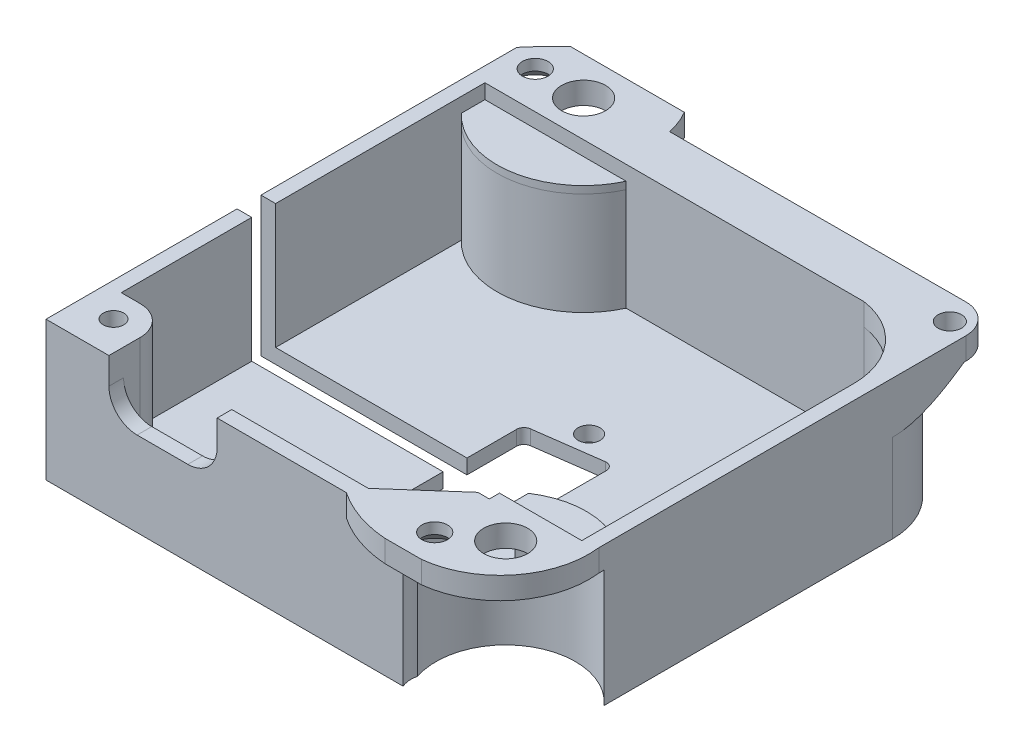
SolidWorks part; units mm, degrees
ref_plane "Спереди" through (0, 0, 0) normal (0, 0, 1) x (1, 0, 0)
ref_plane "Сверху" through (0, 0, 0) normal (0, 1, 0) x (1, 0, 0)
ref_plane "Справа" through (0, 0, 0) normal (1, 0, 0) x (0, 0, -1)
sketch "Sketch1" plane through (0, -19.7, 0) normal (0, 1, 0) x (1, 0, 0)
  line L0 (-32.5, -24.6) -> (-32.5, -32.9854)
  line L1 (-32.5, -32.9854) -> (7.4639, -32.9854)
  line L2 (7.4639, -32.9854) -> (16.9694, -24.6)
  line L45 (28.1923, 12.3774) -> (28.1923, -24.6)
  line L46 (28.1923, -24.6) -> (16.9694, -24.6)
  line L52 (14.473, -37.75) -> (19.5, -37.75)
  line L53 (30.1923, -24.25) -> (30.1923, 29.8047)
  line L54 (30.1923, 29.8047) -> (-14.1412, 29.6964)
  line L55 (-15.4145, 32.9914) -> (-30.9271, 32.9914)
  line L56 (-34.5, 29.2347) -> (-34.5, -5.6693)
  line L57 (-34.5, -5.6693) -> (-32.5, -5.6693)
  line L58 (-32.5, -5.6693) -> (-32.5, 22.8774)
  line L59 (-32.5, 22.8774) -> (19.1923, 22.8774)
  line L87 (-34.5, -34.9854) -> (6.4639, -34.9854)
  line L90 (-32.5, -24.6) -> (-32.5, -8.9249)
  line L91 (-32.5, -8.9249) -> (-34.5, -8.9249)
  line L92 (-34.5, -8.9249) -> (-34.5, -34.9854)
  arc A0 (14.473, -37.75) -> (6.4639, -34.9854) centre (15.6402, -21.385) cw
  circle A1 centre (27.4031, 26.3884) radius 1.6
  circle A10 centre (-23.9566, 27.7968) radius 3
  circle A11 centre (-30.7077, 27.9532) radius 1.75
  circle A12 centre (23.0406, -29.8242) radius 3
  circle A13 centre (17.1804, -33.65) radius 1.75
  arc A15 (19.5, -37.75) -> (30.1923, -24.25) centre (18.1591, -25.7037) ccw
  arc A17 (-14.1412, 29.6964) -> (-15.4145, 32.9914) centre (-23.9566, 27.7968) ccw
  arc A18 (-30.9271, 32.9914) -> (-34.5, 29.2347) centre (0, 0) ccw
  arc A19 (28.1923, 12.3774) -> (19.1923, 22.8774) centre (17.6928, 12.485) ccw
  dimension "D2" = 6
  dimension "D3" = 2
  dimension "D4" = 2
  dimension "D6" = 2
extrude "Boss-Extrude1" add sketch "Sketch1" against normal blind 3
sketch "Sketch2" plane through (0, -22.7, 0) normal (0, -1, 0) x (1, 0, 0)
  line L0 (-34.5, -25.75) -> (20.1923, -25.75)
  line L1 (-34.5, -29.2347) -> (-34.5, 5.6693) construction
  line L2 (30.1923, 24.25) -> (30.1923, -29.8047) construction
  line L3 (-32.5, 24.6) -> (-32.5, 32.9854)
  line L4 (19.1923, -22.8774) -> (-32.5, -22.8774)
  line L5 (-32.5, 32.9854) -> (7.4639, 32.9854)
  line L6 (-32.5, -22.8774) -> (-32.5, 5.6693)
  line L7 (16.9694, 24.6) -> (7.4639, 32.9854) construction
  line L8 (-32.5, 5.6693) -> (-34.5, 5.6693)
  line L9 (-34.5, 5.6693) -> (-34.5, -25.75)
  line L10 (30.1923, -15.75) -> (30.1923, 25.1)
  line L11 (28.1923, -13.8774) -> (28.1923, 24.6)
  line L12 (7.4639, 32.9854) -> (-32.5, 32.9854) construction
  line L13 (7.4639, 32.9854) -> (16.9694, 24.6)
  line L14 (16.9694, 24.6) -> (28.1923, 24.6)
  line L16 (-32.5, 24.6) -> (-32.5, 8.9249)
  line L17 (-32.5, 8.9249) -> (-34.5, 8.9249)
  line L18 (-34.5, 8.9249) -> (-34.5, 34.9854) construction
  line L20 (-34.5, 8.9249) -> (-34.5, 34.9854)
  line L21 (-34.5, 34.9854) -> (6.4639, 34.9854) construction
  line L22 (30.1923, 25.1) -> (30.1923, 26.25)
  line L23 (-34.5, 34.9854) -> (30.1923, 34.9854)
  line L24 (30.1923, 34.9854) -> (30.1923, 26.25)
  arc A0 (20.1923, -25.75) -> (30.1923, -15.75) centre (20.1923, -15.75) ccw
  arc A1 (28.1923, -13.8774) -> (19.1923, -22.8774) centre (19.1923, -13.8774) cw
extrude "Boss-Extrude2" add sketch "Sketch2" along normal blind 14
sketch "Sketch3" plane through (0, -36.7, 0) normal (0, -1, 0) x (1, 0, 0)
  line L15 (-6.3971, 15.146) -> (-6.3971, 8.9249)
  line L16 (3.4678, 17.3642) -> (-5.5322, 16.1369)
  line L17 (4.6029, -2.3354) -> (4.6029, 16.3733)
  line L18 (-5.5322, -2.099) -> (3.4678, -3.3263)
  line L19 (-6.3971, 5.6693) -> (-6.3971, -1.1082)
  line L36 (-34.5, 5.6693) -> (-34.5, -25.75)
  line L37 (-34.5, -25.75) -> (20.1923, -25.75)
  line L38 (30.1923, -15.75) -> (30.1923, 34.9854)
  line L39 (30.1923, 34.9854) -> (-34.5, 34.9854)
  line L40 (-34.5, 34.9854) -> (-34.5, 8.9249)
  line L41 (-34.5, 8.9249) -> (-6.3971, 8.9249)
  line L47 (-6.3971, 5.6693) -> (-34.5, 5.6693)
  arc A6 (20.1923, -25.75) -> (30.1923, -15.75) centre (20.1923, -15.75) ccw
  arc A13 (-5.5322, 16.1369) -> (-6.3971, 15.146) centre (-5.3971, 15.146) ccw
  arc A14 (4.6029, 16.3733) -> (3.4678, 17.3642) centre (3.6029, 16.3733) ccw
  arc A15 (3.4678, -3.3263) -> (4.6029, -2.3354) centre (3.6029, -2.3354) ccw
  arc A16 (-6.3971, -1.1082) -> (-5.5322, -2.099) centre (-5.3971, -1.1082) ccw
  circle A38 centre (-0.8971, -5.4811) radius 1.5
  circle A41 centre (-0.8971, 19.5189) radius 1.5
extrude "Boss-Extrude3" add sketch "Sketch3" along normal blind 2
sketch "Sketch16" plane through (0, -36.7, 0) normal (0, 1, 0) x (1, 0, 0)
  line L2 (28.1923, -20.1051) -> (28.1923, -21.8423)
  line L3 (12.0418, -29.9854) -> (13.542, -29.9854)
  arc A0 (28.1923, -21.8423) -> (13.542, -29.9854) centre (23.0406, -29.8242) ccw
  arc A2 (12.0418, -29.9854) -> (28.1923, -20.1051) centre (23.0406, -29.8242) cw
extrude "Boss-Extrude26" add sketch "Sketch16" along normal up to surface (14 mm away) up to face at (24.3136, -22.7, -18.5705)
sketch "Sketch17" plane through (0, -22.7, 0) normal (0, 1, 0) x (1, 0, 0)
  line L0 (12.0783, -28.9148) -> (16.9694, -28.9148)
  line L2 (16.9694, -28.9148) -> (16.9694, -24.6)
  line L3 (16.9694, -24.6) -> (28.1923, -24.6)
  line L4 (28.1923, -24.6) -> (28.1923, -20.1051)
  arc A3 (28.1923, -20.1051) -> (12.0783, -28.9148) centre (23.0406, -29.8242) ccw
extrude "Boss-Extrude27" add sketch "Sketch17" along normal blind 1
sketch "Sketch4" plane through (0, -22.7, 0) normal (0, -1, 0) x (1, 0, 0)
  circle A0 centre (23.0406, 29.8242) radius 9.5
  circle A1 centre (-23.9566, -27.7968) radius 9.7968
extrude "Cut-Extrude1" cut sketch "Sketch4" along normal blind 30
sketch "Sketch5" plane through (0, 0, 34.9854) normal (0, 0, 1) x (1, 0, 0)
  line L0 (8.9694, -30.7) -> (8.9694, -19.7)
  line L1 (-34.5, -19.7) -> (6.4639, -19.7) construction
  line L2 (16.9694, -30.7) -> (16.9694, -19.7)
  line L3 (14.473, -19.7) -> (19.5, -19.7) construction
  line L4 (16.9694, -19.7) -> (8.9694, -19.7)
  line L5 (10.9694, -32.7) -> (14.9694, -32.7)
  arc A0 (16.9694, -30.7) -> (14.9694, -32.7) centre (14.9694, -30.7) cw
  arc A1 (10.9694, -32.7) -> (8.9694, -30.7) centre (10.9694, -30.7) cw
extrude "Cut-Extrude2" cut sketch "Sketch5" against normal blind 30 from offset 9 offset against normal yes
sketch "Sketch8" plane through (0, 0, 34.9854) normal (0, 0, 1) x (1, 0, 0)
  line L0 (-22.0726, -27.1711) -> (-15.1513, -27.1711)
  line L1 (-11.1572, -23.3874) -> (-11.1572, -19.5274)
  line L2 (-11.1572, -19.5274) -> (-25.9195, -19.5274)
  line L3 (-25.9195, -19.5274) -> (-25.9195, -23.3242)
  arc A0 (-15.1513, -27.1711) -> (-11.1572, -23.3874) centre (-15.1513, -23.1711) ccw
  arc A1 (-22.0726, -27.1711) -> (-25.9195, -23.3242) centre (-22.0726, -23.3242) cw
  point P8 (0, 0)
  point P9 (-11.1572, -24.5907)
  point P10 (-15.1513, -28.3743)
extrude "Cut-Extrude3" cut sketch "Sketch8" against normal blind 10
sketch "Sketch12" plane through (0, -19.7, 0) normal (0, 1, 0) x (1, 0, 0)
  line L1 (-32.5, -32.9854) -> (-25.9195, -32.9854)
  line L2 (-32.5, -32.9854) -> (-32.5, -26.7188)
  line L3 (-32.5, -26.7188) -> (-25.9195, -26.7188)
  line L4 (-25.9195, -32.9854) -> (-25.9195, -26.7188)
  circle A0 centre (-29.9235, -30.3519) radius 1.4
extrude "Boss-Extrude21" add sketch "Sketch12" against normal up to next
chamfer "Chamfer1" distance 4 angle 45 2 edges at (27.2633, -22.7, -22.8211) (2.9082, -22.7, -25.75)
chamfer "Chamfer3" distance 1.5 angle 45 2 edges at (-30.7077, -22.7, -26.2032) (17.1804, -22.7, 35.4)
sketch "Sketch13" plane through (0, -22.7, 0) normal (0, -1, 0) x (1, 0, 0)
  circle A0 centre (27.4031, -26.3884) radius 2.5
  circle A1 centre (17.1804, 33.65) radius 3.25
extrude "Cut-Extrude4" cut sketch "Sketch13" along normal blind 21
fillet "Fillet1" radius 4 1 edges at (30.1923, -21.2, -29.8047)
fillet "Fillet2" radius 4 1 edges at (-25.9195, -28.2, 26.7188)
sketch "Sketch14" plane through (0, -36.7, 0) normal (0, 1, 0) x (1, 0, 0)
  line L0 (19.1923, 22.8774) -> (-15.4844, 22.8774) construction
  line L1 (-32.5, 22.8774) -> (-32.5, -5.6693) construction
  line L2 (-13.2344, 22.8774) -> (-15.4844, 22.8774)
  line L3 (-32.5, 19.662) -> (-32.4287, 22.8774)
  arc A1 (-13.2344, 22.8774) -> (-32.5, 19.662) centre (-23.9566, 27.7968) cw
  arc A2 (-32.4287, 22.8774) -> (-15.4844, 22.8774) centre (-23.9566, 27.7968) ccw
  arc A3 (-32.4287, 22.8774) -> (-15.4844, 22.8774) centre (-23.9566, 27.7968) ccw
  dimension "D2" = 2
  dimension "D1" = 0
extrude "Boss-Extrude23" add sketch "Sketch14" along normal up to surface (14 mm away) separate body up to face at (-30.7077, -22.7, -24.7032)
sketch "Sketch15" plane through (0, -22.7, 0) normal (0, 1, 0) x (1, 0, 0)
  line L0 (-32.5, 19.662) -> (-32.5, 22.8774)
  line L1 (-32.5, 22.8774) -> (-13.2344, 22.8774)
  arc A2 (-32.5, 19.662) -> (-13.2344, 22.8774) centre (-23.9566, 27.7968) ccw
  arc A3 (-32.5, 19.662) -> (-13.2344, 22.8774) centre (-23.9566, 27.7968) ccw
  dimension "D1" = 0
extrude "Boss-Extrude25" add sketch "Sketch15" along normal blind 1 separate body
